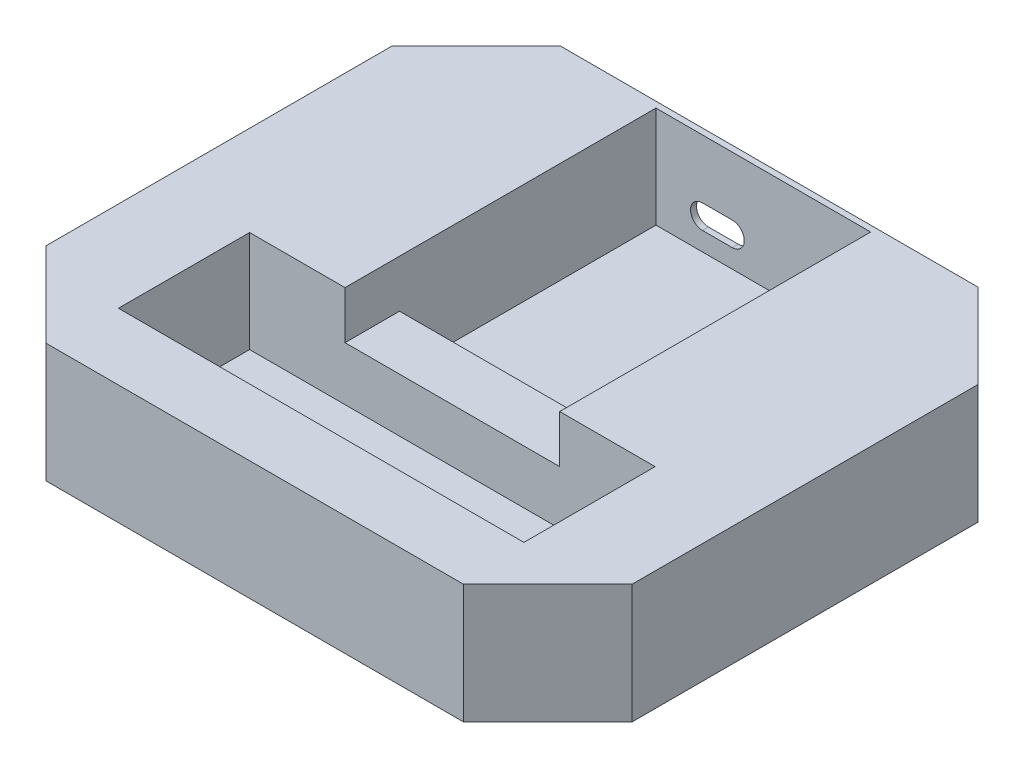
SolidWorks part; units mm, degrees
ref_plane "Front Plane" through (0, 0, 0) normal (0, 0, 1) x (1, 0, 0)
ref_plane "Top Plane" through (0, 0, 0) normal (0, 1, 0) x (1, 0, 0)
ref_plane "Right Plane" through (0, 0, 0) normal (1, 0, 0) x (0, 0, -1)
sketch "Sketch1" plane through (0, 0, 0) normal (0, 1, 0) x (1, 0, 0)
  line L0 (-35, 43.1421) -> (35, 43.1421)
  line L1 (35, 43.1421) -> (49.1421, 29)
  line L2 (49.1421, 29) -> (49.1421, -29)
  line L3 (49.1421, -29) -> (35, -43.1421)
  line L4 (35, -43.1421) -> (-35, -43.1421)
  line L5 (-35, -43.1421) -> (-49.1421, -29)
  line L6 (-49.1421, -29) -> (-49.1421, 29)
  line L7 (-49.1421, 29) -> (-35, 43.1421)
  line L8 (-49.1421, 0) -> (49.1421, 0) construction
  line L9 (0, 43.1421) -> (0, -43.1421) construction
  point P12 (0, 0)
  dimension "D1" = 70
  dimension "D2" = 20
  dimension "D3" = 58
  dimension "D4" = 135
extrude "Boss-Extrude1" add sketch "Sketch1" along normal blind 20
sketch "Sketch2" plane through (0, 20, 0) normal (0, 1, 0) x (1, 0, 0)
  line L0 (35, 43.1421) -> (-35, 43.1421) construction
  line L1 (-18, 42.1421) -> (18, 42.1421)
  line L2 (-18, 42.1421) -> (-18, -0.8579)
  line L3 (-18, -0.8579) -> (18, -0.8579)
  line L4 (18, 42.1421) -> (18, -0.8579)
  line L5 (-18, 42.1421) -> (18, -0.8579) construction
  line L6 (-18, -0.8579) -> (18, 42.1421) construction
  line L8 (-34, -10) -> (34, -10)
  line L9 (-34, -10) -> (-34, -32)
  line L10 (-34, -32) -> (34, -32)
  line L11 (34, -10) -> (34, -32)
  line L12 (-34, -10) -> (34, -32) construction
  line L13 (-34, -32) -> (34, -10) construction
  point P0 (0, 20.6421)
  point P5 (0, 0)
  point P6 (0, 0)
  point P10 (0, -21)
  dimension "D1" = 36
  dimension "D2" = 43
  dimension "D3" = 1
  dimension "D4" = 68
  dimension "D5" = 22
  dimension "D6" = 10
extrude "Cut-Extrude1" cut sketch "Sketch2" against normal blind 17
sketch "Sketch3" plane through (0, 20, 0) normal (0, 1, 0) x (1, 0, 0)
  line L0 (34, -10) -> (-34, -10) construction
  line L1 (-18, -10) -> (18, -10)
  line L2 (-18, -10) -> (-18, -0.8579)
  line L3 (-18, -0.8579) -> (18, -0.8579)
  line L4 (18, -10) -> (18, -0.8579)
  line L5 (-18, -10) -> (18, -0.8579) construction
  line L6 (-18, -0.8579) -> (18, -10) construction
  point P0 (0, -5.4289)
  dimension "D1" = 36
extrude "Cut-Extrude2" cut sketch "Sketch3" against normal blind 8
sketch "Sketch4" plane through (0, 0, -42.1421) normal (0, 0, 1) x (1, 0, 0)
  line L0 (-10.2, 8.13) -> (-5.2, 8.13) construction
  line L1 (-10.2, 10.13) -> (-5.2, 10.13)
  line L2 (-10.2, 6.13) -> (-5.2, 6.13)
  line L3 (18, 3) -> (-18, 3) construction
  line L4 (-18, 3) -> (-18, 20) construction
  arc A0 (-10.2, 10.13) -> (-10.2, 6.13) centre (-10.2, 8.13) ccw
  arc A1 (-5.2, 6.13) -> (-5.2, 10.13) centre (-5.2, 8.13) ccw
  point P2 (-7.7, 8.13)
  point P7 (-12.2, 8.13)
  point P8 (-3.2, 8.13)
  dimension "D2" = 9
  dimension "D4" = 5.8
  dimension "D1" = 4
  dimension "D3" = 3.13
extrude "Cut-Extrude3" cut sketch "Sketch4" against normal up to next
